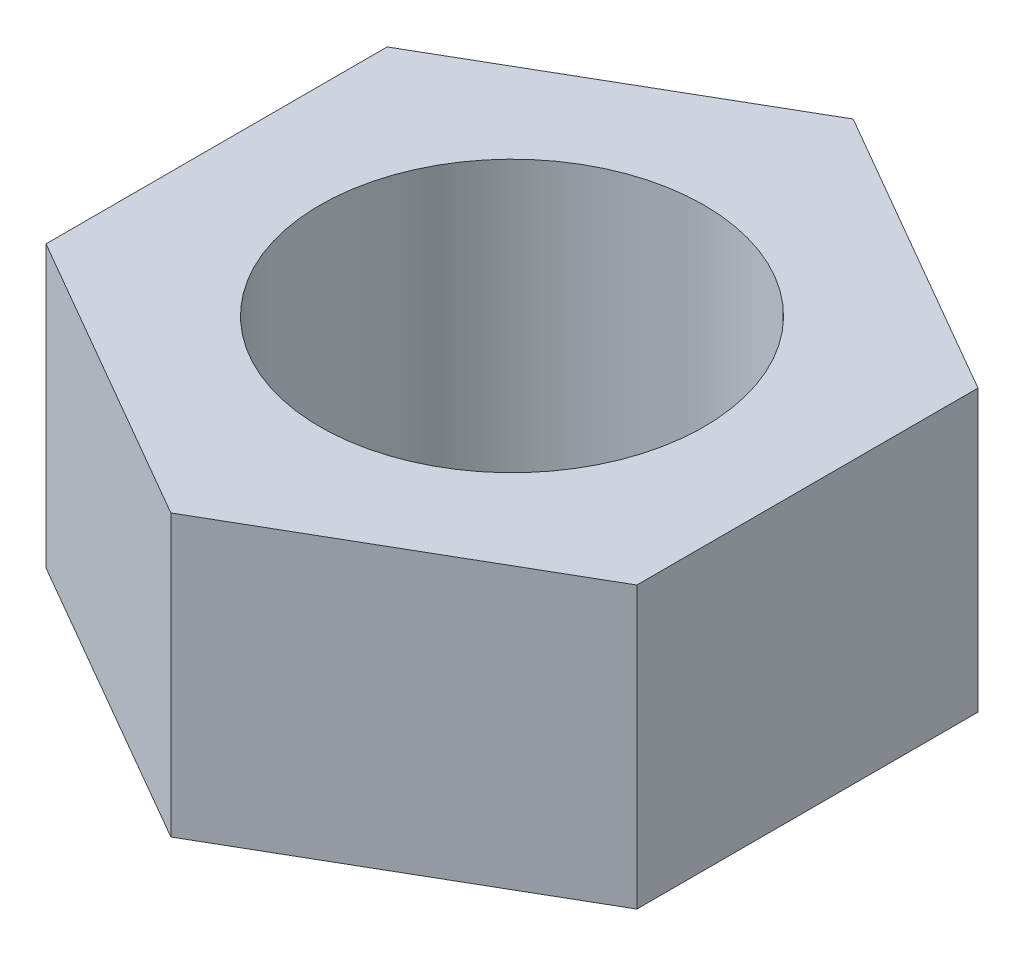
SolidWorks part; units mm, degrees
ref_plane "Спереди" through (0, 0, 0) normal (0, 0, 1) x (1, 0, 0)
ref_plane "Сверху" through (0, 0, 0) normal (0, 1, 0) x (1, 0, 0)
ref_plane "Справа" through (0, 0, 0) normal (1, 0, 0) x (0, 0, -1)
sketch "Эскиз1" plane through (0, 0, 0) normal (0, 1, 0) x (1, 0, 0)
  line L1 (4, -2.3094) -> (4, 2.3094)
  line L2 (4, 2.3094) -> (0, 4.6188)
  line L3 (0, 4.6188) -> (-4, 2.3094)
  line L4 (-4, 2.3094) -> (-4, -2.3094)
  line L5 (-4, -2.3094) -> (0, -4.6188)
  line L6 (0, -4.6188) -> (4, -2.3094)
  circle A0 centre (0, 0) radius 4 construction
  circle A1 centre (0, 0) radius 2.6
extrude "Бобышка-Вытянуть1" add sketch "Эскиз1" along normal blind 3.8
